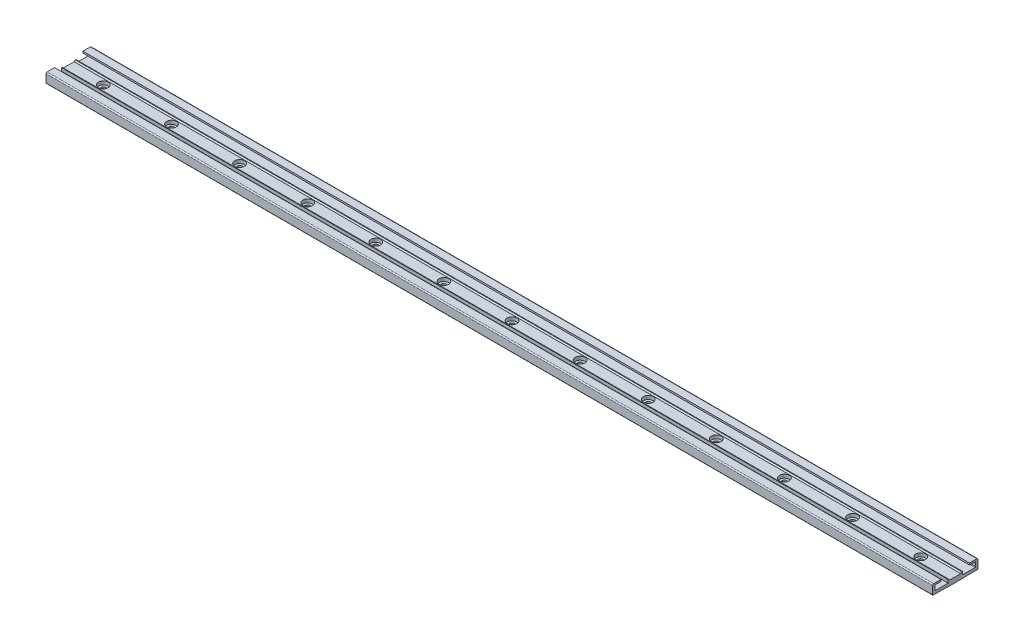
SolidWorks part; units mm, degrees
material "6061-T6 (SS)"
ref_plane "Front" through (0, 0, 0) normal (0, 0, 1) x (1, 0, 0)
ref_plane "Top" through (0, 0, 0) normal (0, 1, 0) x (1, 0, 0)
ref_plane "Right" through (0, 0, 0) normal (1, 0, 0) x (0, 0, -1)
sketch "Sketch1" plane through (0, 0, 0) normal (1, 0, 0) x (0, 0, -1)
  line L0 (-8, 0.2) -> (-8, 0)
  line L1 (-8, 0) -> (8, 0)
  line L2 (8, 0) -> (8, 0.2)
  line L3 (8, 0.2) -> (19.5, 0.2)
  line L4 (20, 0.7) -> (20, 7.7)
  line L5 (19, 8.7) -> (12.5, 8.7)
  line L6 (12.5, 8.7) -> (12.5, 7.2)
  line L7 (12.5, 7.2) -> (17.5, 7.2)
  line L8 (18, 6.7) -> (18, 3.3)
  line L9 (17.5, 2.8) -> (6.3, 2.8)
  line L10 (6.3, 2.8) -> (6.3, 5.5)
  line L11 (6.3, 5.5) -> (5.75, 5.5)
  line L12 (5.75, 5.5) -> (4.75, 4.5)
  line L13 (4.75, 4.5) -> (-4.75, 4.5)
  line L14 (-4.75, 4.5) -> (-5.75, 5.5)
  line L15 (-5.75, 5.5) -> (-6.3, 5.5)
  line L16 (-6.3, 5.5) -> (-6.3, 2.8)
  line L17 (-6.3, 2.8) -> (-17.5, 2.8)
  line L18 (-18, 3.3) -> (-18, 6.7)
  line L19 (-17.5, 7.2) -> (-12.5, 7.2)
  line L20 (-12.5, 7.2) -> (-12.5, 8.7)
  line L21 (-12.5, 8.7) -> (-19, 8.7)
  line L22 (-20, 7.7) -> (-20, 0.7)
  line L23 (-19.5, 0.2) -> (-8, 0.2)
  arc A0 (19.5, 0.2) -> (20, 0.7) centre (19.5, 0.7) ccw
  arc A1 (20, 7.7) -> (19, 8.7) centre (19, 7.7) ccw
  arc A2 (18, 6.7) -> (17.5, 7.2) centre (17.5, 6.7) ccw
  arc A3 (17.5, 2.8) -> (18, 3.3) centre (17.5, 3.3) ccw
  arc A4 (-18, 3.3) -> (-17.5, 2.8) centre (-17.5, 3.3) ccw
  arc A5 (-17.5, 7.2) -> (-18, 6.7) centre (-17.5, 6.7) ccw
  arc A6 (-19, 8.7) -> (-20, 7.7) centre (-19, 7.7) ccw
  arc A7 (-20, 0.7) -> (-19.5, 0.2) centre (-19.5, 0.7) ccw
extrude "Boss-Extrude1" add sketch "Sketch1" along normal blind 781.05
hole_wizard "CBORE for M4 SBHCS1" positions "Sketch2" profile "Sketch3" counterbore size "M4" standard "ANSI Metric" end condition through all
sketch "Sketch2" plane through (0, 4.5, 0) normal (0, 1, 0) x (1, 0, 0)
  line L1 (30.525, 0) -> (0, 0) construction
  line L3 (781.05, 0) -> (750.525, 0) construction
  line L4 (781.05, 4.75) -> (781.05, -4.75) construction
  point P0 (30.525, 0)
  dimension "D1" = 720
sketch "Sketch3" plane through (30.525, 4.5, 0) normal (1, 0, 0) x (0, 0, 1)
  line L0 (0, 0) -> (0, 4.5)
  line L1 (0, 4.5) -> (2.25, 4.5)
  line L3 (2.25, 4.5) -> (2.25, 3.1)
  line L4 (2.25, 3.1) -> (4.3, 3.1)
  line L5 (4.3, 3.1) -> (4.3, 0)
  line L7 (4.3, 0) -> (0, 0)
  line L11 (0, -6.35) -> (0, 107.95) construction
  dimension "Thru Hole Dia." = 4.5
  dimension "Thru Hole Depth" = 4.5
  dimension "C'Bore Dia." = 8.6
  dimension "C'Bore Depth" = 3.1
pattern_linear "LPattern1" count 13 spacing 60 along (1, 0, 0) of "CBORE for M4 SBHCS1"
equation "\"END\"= int ( \"RD1@Annotations\" / 60 )"
equation "\"D1@Sketch2\"=(\"END\"-1)*60"
